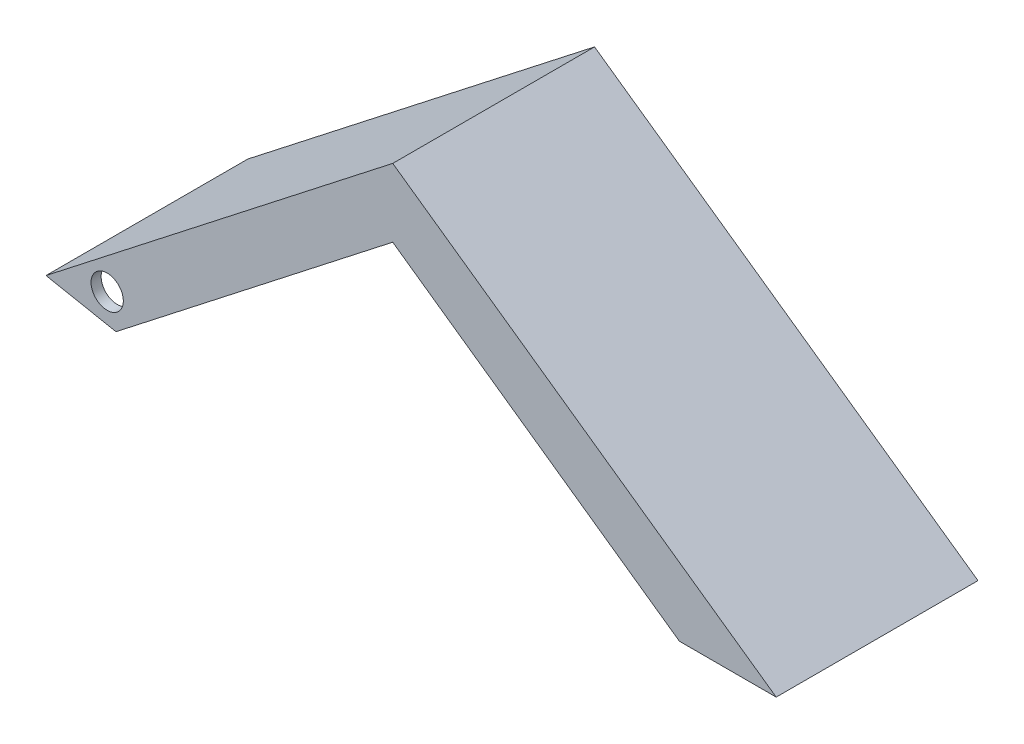
SolidWorks part; units mm, degrees
ref_plane "Front Plane" through (0, 0, 0) normal (0, 0, 1) x (1, 0, 0)
ref_plane "Top Plane" through (0, 0, 0) normal (0, 1, 0) x (1, 0, 0)
ref_plane "Right Plane" through (0, 0, 0) normal (1, 0, 0) x (0, 0, -1)
sketch "Sketch1" plane through (0, 0, 0) normal (0, 0, 1) x (1, 0, 0)
  line L0 (0, 0) -> (17.1816, 13.4031)
  line L1 (17.1816, 13.4031) -> (36.1827, 0)
  line L2 (36.1827, 0) -> (31.3881, 0)
  line L3 (31.3881, 0) -> (17.1816, 10.021)
  line L4 (17.1816, 10.021) -> (3.4691, -0.6759)
  line L5 (3.4691, -0.6759) -> (0, 0)
extrude "Boss-Extrude1" add sketch "Sketch1" along normal blind 10 contours L0 L1 L2 L3 L4 L5
sketch "Sketch3" plane through (0, 0, 10) normal (0, 0, 1) x (1, 0, 0)
  circle A0 centre (3.0315, 0.8223) radius 0.8
extrude "Cut-Extrude1" cut sketch "Sketch3" against normal blind 10
shell "Shell3" thickness 0.5 removed face at (3.8315, 0.8223, 0) removed face at (1.7345, -0.338, 5)
